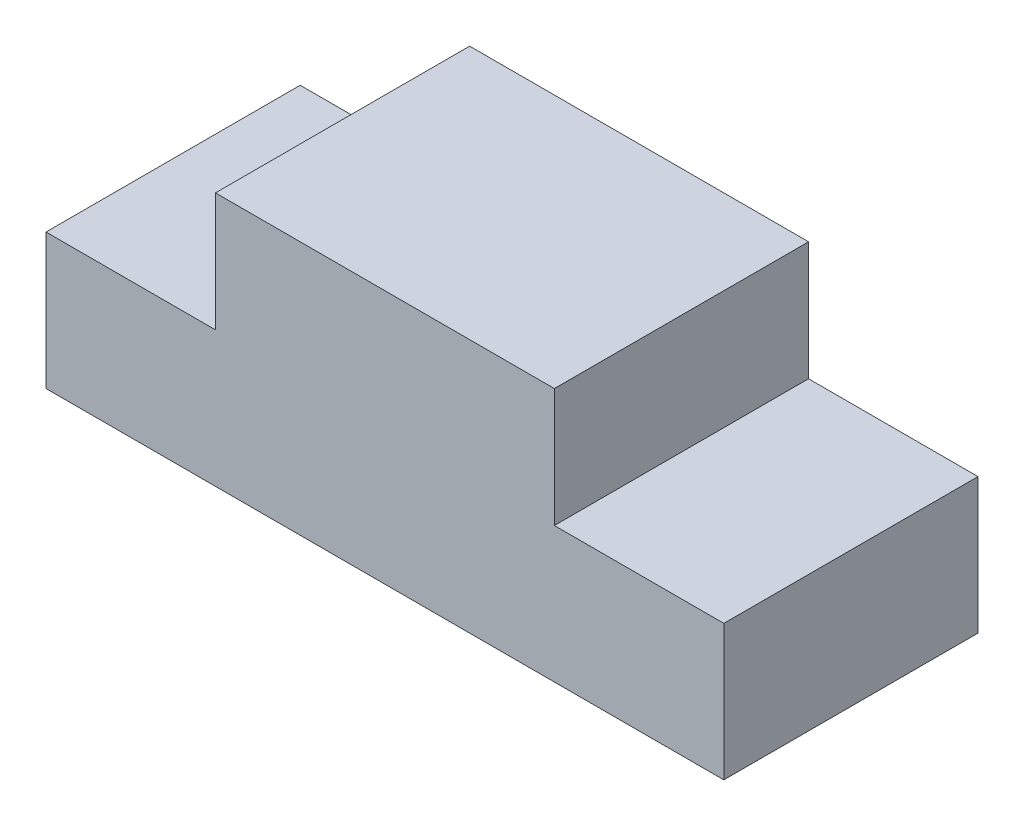
SolidWorks part; units mm, degrees
ref_plane "Front Plane" through (0, 0, 0) normal (0, 0, 1) x (1, 0, 0)
ref_plane "Top Plane" through (0, 0, 0) normal (0, 1, 0) x (1, 0, 0)
ref_plane "Right Plane" through (0, 0, 0) normal (1, 0, 0) x (0, 0, -1)
sketch "Sketch1" plane through (0, 0, 0) normal (0, 0, 1) x (1, 0, 0)
  line L0 (0, 0) -> (40, 0)
  line L1 (40, 0) -> (40, 8)
  line L2 (40, 8) -> (30, 8)
  line L3 (30, 8) -> (30, 15)
  line L4 (30, 15) -> (10, 15)
  line L5 (10, 15) -> (10, 8)
  line L6 (10, 8) -> (0, 8)
  line L7 (0, 8) -> (0, 0)
  dimension "D1" = 8
  dimension "D2" = 15
  dimension "D3" = 20
  dimension "D4" = 40
extrude "Boss-Extrude1" add sketch "Sketch1" along normal blind 15
hole_wizard "Tap Drill for M10 Tap1" positions "Sketch3" profile "Sketch2" hole size "M10" standard "ISO"
sketch "Sketch3" plane through (0, 0, 0) normal (0, 0, -1) x (-1, 0, 0)
  line L0 (-30, 15) -> (-10, 15) construction
  line L1 (-30, 8) -> (-30, 15) construction
  point P0 (-20, 9)
  dimension "D1" = 6
  dimension "D2" = 10
sketch "Sketch2" plane through (20, 9, 0) normal (1, 0, 0) x (0, 1, 0)
  line L0 (0, 0) -> (0, 13.5537)
  line L1 (0, 13.5537) -> (4.25, 11)
  line L2 (4.25, 11) -> (4.25, 0)
  line L5 (4.25, 0) -> (0, 0)
  line L10 (0, 13.5537) -> (-4.25, 11) construction
  line L11 (0, -6.35) -> (0, 107.95) construction
  dimension "Hole Dia." = 8.5
  dimension "Hole Depth" = 11
  dimension "Drill Angle" = 118
